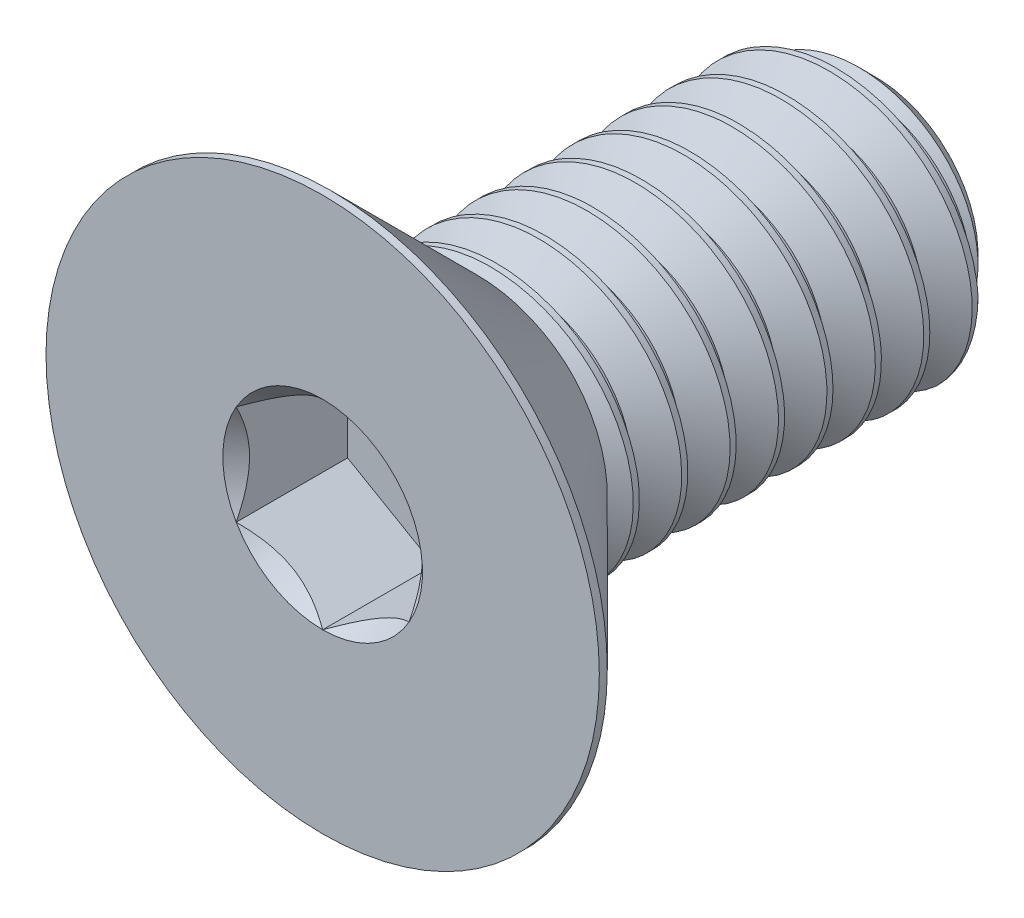
SolidWorks part; units mm, degrees
ref_plane "Front" through (0, 0, 0) normal (0, 0, 1) x (1, 0, 0)
ref_plane "Top" through (0, 0, 0) normal (0, 1, 0) x (1, 0, 0)
ref_plane "Right" through (0, 0, 0) normal (1, 0, 0) x (0, 0, -1)
sketch "Sketch11" plane through (0, 0, 0) normal (1, 0, 0) x (0, 0, -1)
  line L0 (-4, 4) -> (4, 4) construction
  line L5 (-4, 4) -> (-4, -4) construction
  line L6 (4, 2) -> (4, -2) construction
  line L7 (-3.99, 1.25) -> (-3.99, -1.25) construction
  line L8 (3.9562, 2.0758) -> (4.6563, 2.0758) construction
  line L9 (4.6563, 2.0758) -> (4.3062, 1.4696) construction
  line L10 (4.3062, 1.4696) -> (3.9562, 2.0758) construction
  line L11 (4.2625, 1.5453) -> (4.35, 1.5453) construction
  line L12 (4.3062, 1.5453) -> (4.3062, 1.4696) construction
  line L13 (3.9781, 2.0379) -> (4.6344, 2.0379) construction
  line L14 (4.3062, 2.0758) -> (4.3062, 2) construction
  line L15 (4, 2) -> (4.6125, 2) construction
  line L17 (-3.885, 4) -> (0.115, 0) construction
  line L18 (0.115, 0) -> (-3.885, -4) construction
  point P3 (-1.7, 4)
  point P8 (0, 4)
  point P21 (4.3062, 2.0379)
  point P26 (-4, 0)
  point P28 (-3.99, 0)
  point P29 (4, 0)
  dimension "Length" = 8
  dimension "Head Diameter" = 8
  dimension "Thread Major Diameter" = 4
  dimension "Head Height" = 2.3
  dimension "Drive Size" = 2.5
  dimension "Thread Pitch" = 0.7
  dimension "D1" = 0.0875
  dimension "D2" = 0.01
  dimension "D3" = 0.115
  dimension "Countersink Angle" = 90
sketch "Sketch1" plane through (0, 0, 0) normal (1, 0, 0) x (0, 0, -1)
  line L2 (-1.7, 2) -> (4, 2)
  line L3 (4, 2) -> (4, 0)
  line L4 (-2.39, 2) -> (-2.39, 0)
  line L5 (-1.7, 2) -> (-2.39, 2)
  line L6 (-4, 4) -> (-4, -4) construction
  line L7 (4, 2) -> (4, -2) construction
  line L8 (-2.39, 0) -> (4, 0)
  dimension "D1" = 1.61
revolve "Revolve1" add sketch "Sketch1" angle 360 mid plane about L8
chamfer "Chamfer1" distance 0.525 angle 45 1 edges at (0, -2, -4)
sketch "Sketch7" plane through (0, 0, 0) normal (1, 0, 0) x (0, 0, -1)
  line L2 (-4, 4) -> (-3.885, 4)
  line L5 (-1.7, 1.815) -> (-1.7, 0)
  line L6 (-4, 4) -> (-4, 0)
  line L8 (-4, 4) -> (-4, -4) construction
  line L9 (-4, 0) -> (-1.7, 0)
  line L12 (-3.885, 4) -> (-1.7, 1.815)
  line L13 (-3.885, 4) -> (0.115, 0) construction
revolve "Revolve2" add sketch "Sketch7" angle 360 mid plane about L9 region at (0, 1.5544, 2.9977)
ref_plane "Plane1" through (0, 0, 1.7) normal (0, 0, 1) x (1, 0, 0)
sketch "Sketch5" plane through (0, 0, 4) normal (0, 0, 1) x (1, 0, 0)
  line L1 (1.25, -0.7217) -> (1.25, 0.7217)
  line L2 (1.25, 0.7217) -> (0, 1.4434)
  line L3 (0, 1.4434) -> (-1.25, 0.7217)
  line L4 (-1.25, 0.7217) -> (-1.25, -0.7217)
  line L5 (-1.25, -0.7217) -> (0, -1.4434)
  line L6 (0, -1.4434) -> (1.25, -0.7217)
  circle A0 centre (0, 0) radius 1.25 construction
extrude "Cut-Extrude2" cut sketch "Sketch5" against normal blind 1.61
sketch "Sketch6" plane through (0, 0, 4) normal (0, 0, -1) x (-1, 0, 0)
  circle A0 centre (0, 0) radius 1.4434
extrude "Cut-Extrude3" cut sketch "Sketch6" along normal blind 1.61 draft 45
sketch "Sketch12" plane through (0, 0, -4) normal (0, 0, -1) x (-1, 0, 0)
  circle A0 centre (0, 0) radius 2 construction
  circle A1 centre (0, 0) radius 2
curve "Helix/Spiral1" pitch 0.7 height 8 radius 2 centre (0, 0, -4) axis (0, 0, 1) start towards (0, 1, 0)
sketch "Sketch13" plane through (0, 0, 0) normal (1, 0, 0) x (0, 0, -1)
  line L0 (3.9781, 2.0379) -> (4.6344, 2.0379)
  line L1 (4.6344, 2.0379) -> (4.35, 1.5453)
  line L2 (4.35, 1.5453) -> (4.2625, 1.5453)
  line L3 (4.2625, 1.5453) -> (3.9781, 2.0379)
sweep "Cut-Sweep1" cut profiles "Sketch13" path "Helix/Spiral1" align with end faces yes
combine bodies "Combine1" operation type add bodies to combine 113 127
equation "\"D1@Chamfer1\"=\"Thread Pitch@Sketch11\" * .75"
equation "\"D1@Cut-Extrude2\"= \"Head Height@Sketch11\" * .7"
equation "\"D1@Cut-Extrude3\" = \"D1@Cut-Extrude2\""
equation "\"D1@Sketch11\"=\"Thread Pitch@Sketch11\"/8"
equation "\"D3@Sketch11\"=\"Head Height@Sketch11\"*.05"
equation "\"D4@Helix/Spiral1\"=\"Thread Pitch@Sketch11\""
equation "\"D1@Sketch1\"=\"Head Height@Sketch11\"*.7"
equation "\"D3@Helix/Spiral1\"=\"Length@Sketch11\""
